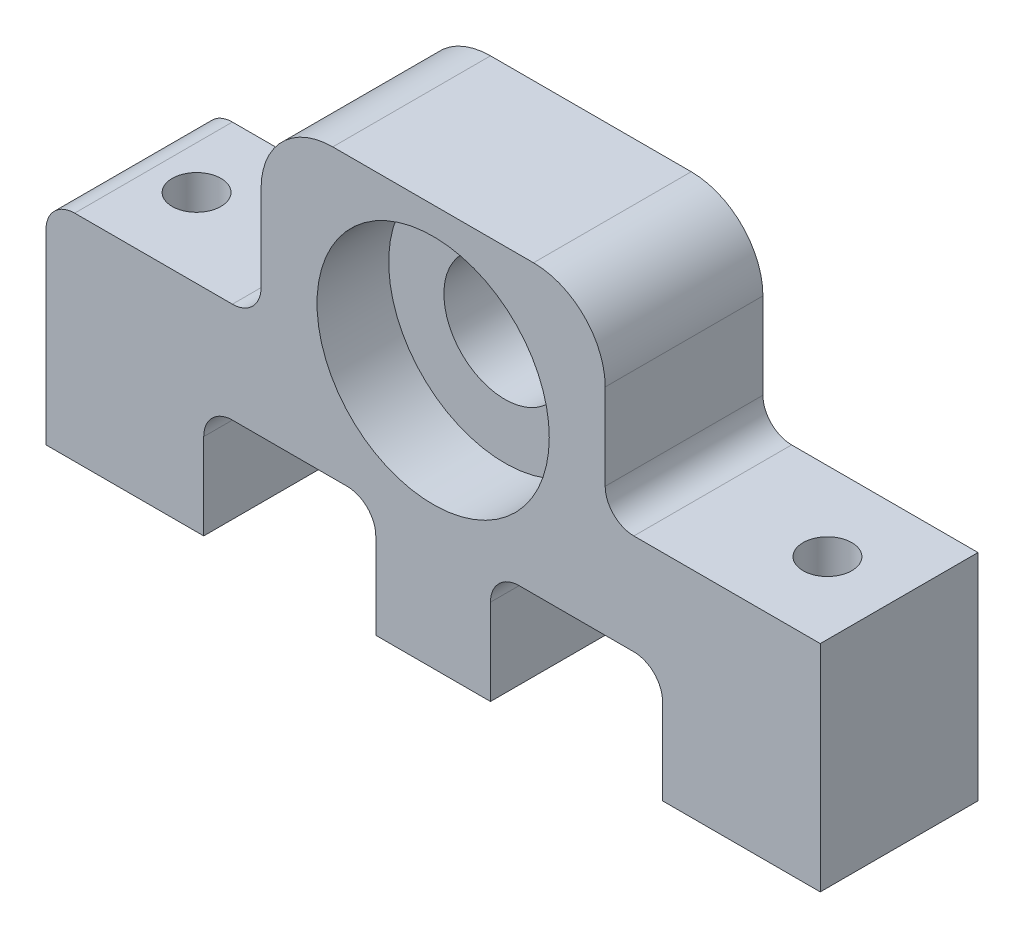
SolidWorks part; units mm, degrees
material "POM 乙缩醛共聚物"
ref_plane "前视基准面" through (0, 0, 0) normal (0, 0, 1) x (1, 0, 0)
ref_plane "上视基准面" through (0, 0, 0) normal (0, 1, 0) x (1, 0, 0)
ref_plane "右视基准面" through (0, 0, 0) normal (1, 0, 0) x (0, 0, -1)
sketch "草图1" plane through (0, 0, 0) normal (0, 0, 1) x (1, 0, 0)
  line L0 (0, 16.8171) -> (0, -19.3149) construction
  line L1 (-12, 14) -> (12, 14)
  line L2 (-12, 14) -> (-12, -14)
  line L3 (-12, -14) -> (12, -14)
  line L4 (12, 14) -> (12, -14)
  line L5 (-12, 14) -> (12, -14) construction
  line L6 (-12, -14) -> (12, 14) construction
  circle A0 centre (0, 4) radius 8 construction
  circle A1 centre (0, 4) radius 4.25
  point P0 (0, 0)
  dimension "D1" = 16
  dimension "D3" = 10
  dimension "D5" = 8.5
  dimension "D2" = 4
  dimension "D4" = 18
extrude "凸台-拉伸1" add sketch "草图1" along normal blind 11
sketch "草图2" plane through (0, 0, 11) normal (0, 0, 1) x (1, 0, 0)
  circle A0 centre (0, 4) radius 8.1
  dimension "D1" = 16.2
extrude "切除-拉伸1" cut sketch "草图2" against normal blind 5
sketch "草图3" plane through (0, 14, 0) normal (0, 1, 0) x (1, 0, 0)
  line L0 (0, 0) -> (0, -18.8293) construction
  line L1 (12, 0) -> (-12, 0) construction
  line L2 (-12, -11) -> (-12, 0) construction
  circle A0 centre (-9, -4) radius 1.6
  circle A1 centre (9, -4) radius 1.6
  dimension "D1" = 3.2
  dimension "D2" = 3
  dimension "D3" = 4
extrude "切除-拉伸2" [suppressed] cut sketch "草图3" against normal through all
sketch "草图6" plane through (0, 0, 11) normal (0, 0, 1) x (1, 0, 0)
  line L0 (-12, 1) -> (-27, 1)
  line L1 (-12, 14) -> (-12, -14) construction
  line L2 (-27, 1) -> (-27, -14)
  line L3 (-27, -14) -> (-12, -14)
  line L4 (-12, -14) -> (-12, 1)
  line L5 (12, 1) -> (12, -14)
  line L6 (12, -14) -> (12, 14) construction
  line L7 (12, -14) -> (27, -14)
  line L8 (27, -14) -> (27, 1)
  line L9 (27, 1) -> (12, 1)
  dimension "D1" = 15
  dimension "D2" = 15
  dimension "D3" = 15
  dimension "D4" = 15
extrude "凸台-拉伸2" add sketch "草图6" against normal up to surface (11 mm away) up to face at (0, 0, 0)
sketch "草图7" plane through (0, 1, 0) normal (0, 1, 0) x (1, 0, 0)
  line L0 (12, 0) -> (27, 0) construction
  line L1 (27, 0) -> (27, -11) construction
  line L2 (-27, 0) -> (-12, 0) construction
  line L3 (-27, 0) -> (-27, -11) construction
  line L4 (0, 0) -> (0, -16.6872) construction
  circle A0 centre (22, -5.5) radius 1.7
  circle A1 centre (-22, -5.5) radius 1.7
  circle A2 centre (-10.5, -5.5) radius 1.7 construction
  circle A3 centre (10.5, -5.5) radius 1.7
  dimension "D1" = 3.4
  dimension "D2" = 3.4
  dimension "D3" = 5.5
  dimension "D4" = 5
  dimension "D5" = 5.5
  dimension "D6" = 5
  dimension "D7" = 16.5
extrude "切除-拉伸3" cut sketch "草图7" against normal through all both and the other way through all
sketch "草图8" plane through (0, 0, 11) normal (0, 0, 1) x (1, 0, 0)
  line L0 (0, 14) -> (0, -14) construction
  line L1 (12, 14) -> (-12, 14) construction
  line L2 (-27, -14) -> (27, -14) construction
  line L4 (-16, -14) -> (-4, -14)
  line L5 (-16, -14) -> (-16, -6)
  line L6 (-16, -6) -> (-4, -6)
  line L7 (-4, -14) -> (-4, -6)
  line L8 (16, -14) -> (4, -14)
  line L9 (16, -14) -> (16, -6)
  line L10 (16, -6) -> (4, -6)
  line L11 (4, -14) -> (4, -6)
  point P15 (-10, -6)
  point P16 (10, -6)
  dimension "D1" = 12
  dimension "D2" = 20
  dimension "D3" = 8
extrude "切除-拉伸4" cut sketch "草图8" against normal through all
fillet "圆角1" radius 2 4 edges at (16, -6, 5.5) (4, -6, 5.5) (-4, -6, 5.5) (-16, -6, 5.5)
fillet "圆角2" radius 2 4 edges at (-27, 1, 5.5) (12, 1, 8.65) (12, 1, 2.35) (-12, 1, 5.5)
fillet "圆角3" radius 5 2 edges at (12, 14, 8.65) (-12, 14, 5.5)
sketch "草图9" plane through (0, -6, 0) normal (0, -1, 0) x (1, 0, 0)
  circle A0 centre (10.5, 5.5) radius 1.7 construction
  circle A1 centre (10.5, 5.5) radius 1.7
extrude "凸台-拉伸3" add sketch "草图9" against normal blind 25
sketch "草图10" plane through (0, 0, 11) normal (0, 0, 1) x (1, 0, 0)
  line L0 (12, 3) -> (12, 9) construction
  line L1 (12, 3) -> (12, 9)
  line L2 (7, 14) -> (7.5942, 21.7946)
  line L3 (7.5942, 21.7946) -> (15.4529, 21.7946)
  line L4 (15.4529, 21.7946) -> (16.4623, 6.8702)
  line L5 (16.4623, 6.8702) -> (14, 1)
  arc A0 (12, 3) -> (14, 1) centre (14, 3) ccw construction
  arc A1 (12, 9) -> (7, 14) centre (7, 9) ccw construction
  arc A2 (12, 3) -> (14, 1) centre (14, 3) ccw
  arc A3 (12, 9) -> (7, 14) centre (7, 9) ccw
extrude "切除-拉伸5" cut sketch "草图10" against normal blind 25
